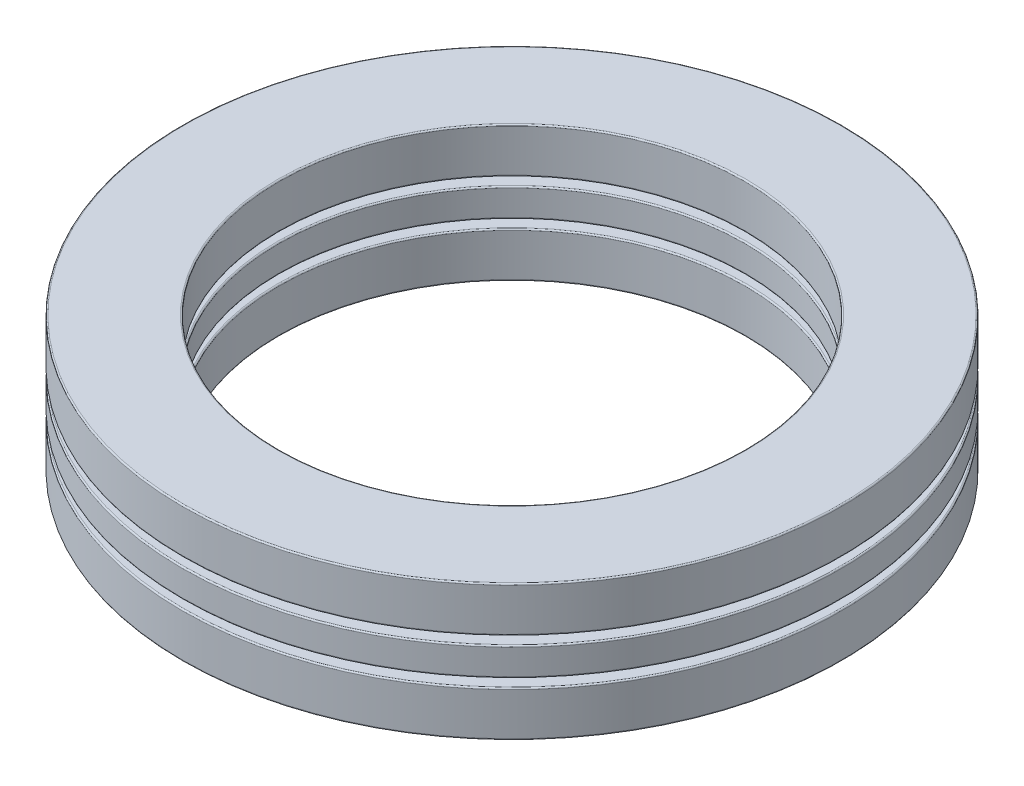
SolidWorks part; units mm, degrees
ref_plane "Front Plane" through (0, 0, 0) normal (0, 0, 1) x (1, 0, 0)
ref_plane "Top Plane" through (0, 0, 0) normal (0, 1, 0) x (1, 0, 0)
ref_plane "Right Plane" through (0, 0, 0) normal (1, 0, 0) x (0, 0, -1)
sketch "Sketch1" plane through (0, 0, 0) normal (1, 0, 0) x (0, 0, -1)
  line L0 (-26.9875, 0) -> (26.9875, 0) construction
  line L1 (0, -5.5499) -> (0, 5.5499) construction
  line L2 (-26.9875, 1.1562) -> (-19.0881, 1.1562)
  line L3 (-26.9875, 1.1562) -> (-26.9875, -1.1562)
  line L4 (-26.9875, -1.1562) -> (-19.0881, -1.1562)
  line L5 (-19.0881, 1.1562) -> (-19.0881, -1.1562)
  line L6 (-23.0378, 1.85) -> (-23.0378, -1.85) construction
  circle A0 centre (-23.0378, 0) radius 1.85 construction
  point P13 (-23.0378, 1.1562)
  dimension "OD" = 53.975
  dimension "Shaft Dia" = 38.1762
  dimension "Th" = 11.0998
  dimension "D1" = 3.6999
  dimension "D2" = 2.3125
revolve "Revolve1" add sketch "Sketch1" angle 360 about L1
sketch "Sketch3" plane through (0, 0, 0) normal (1, 0, 0) x (0, 0, -1)
  line L0 (-23.0378, 1.85) -> (-23.0378, -1.85)
  arc A0 (-23.0378, 1.85) -> (-23.0378, -1.85) centre (-23.0378, 0) ccw
  circle A1 centre (-23.0378, 0) radius 1.85 construction
revolve "Cut-Revolve1" cut sketch "Sketch3" angle 360 about L0
sketch "Sketch2" plane through (0, 0, 0) normal (1, 0, 0) x (0, 0, -1)
  line L0 (-23.0378, 1.85) -> (-23.0378, -1.85)
  arc A0 (-23.0378, 1.85) -> (-23.0378, -1.85) centre (-23.0378, 0) ccw
  circle A2 centre (-23.0378, 0) radius 1.85 construction
revolve "Revolve2" add sketch "Sketch2" angle 360 about L0
ref_axis "Axis1" through (0, 5.5499, 0) along (0, -1, 0)
pattern_circular "CirPattern1" count 11 every 32.727 about axis through (0, 5.5499, 0) along (0, -1, 0) of bodies 187
pattern_circular "CirPattern2" count 11 every 32.727 about axis through (0, 5.5499, 0) along (0, -1, 0) of "Cut-Revolve1"
sketch "Sketch4" plane through (0, 0, 0) normal (1, 0, 0) x (0, 0, -1)
  line L0 (-26.9875, 1.1562) -> (-26.9875, -1.1562) construction
  line L1 (-26.9875, 1.85) -> (-19.0881, 1.85)
  line L2 (-26.9875, 1.85) -> (-26.9875, 5.5499)
  line L3 (-26.9875, 5.5499) -> (-19.0881, 5.5499)
  line L4 (-19.0881, 1.85) -> (-19.0881, 5.5499)
  line L5 (-26.9875, -5.5499) -> (-19.0881, -5.5499)
  line L6 (-26.9875, -5.5499) -> (-26.9875, -1.85)
  line L7 (-26.9875, -1.85) -> (-19.0881, -1.85)
  line L8 (-19.0881, -5.5499) -> (-19.0881, -1.85)
  line L9 (-23.0378, 1.85) -> (-23.0378, -1.85) construction
  line L10 (-19.0881, 1.1562) -> (-19.0881, -1.1562) construction
  line L11 (0, 0) -> (-26.9875, 0) construction
  line L12 (-26.9875, 0) -> (26.9875, 0) construction
  dimension "Ht" = 11.0998
revolve "Revolve3" add sketch "Sketch4" angle 360 about L1
fillet "Fillet1" radius 0.111 4 edges at (0, 1.85, -19.0881) (0, 5.5499, -19.0881) (0, 1.85, -26.9875) (0, 5.5499, -26.9875)
fillet "Fillet2" radius 0.111 4 edges at (0, -1.1562, -19.0881) (0, 1.1562, -19.0881) (0, -1.1562, -26.9875) (0, 1.1562, -26.9875)
fillet "Fillet3" radius 0.111 4 edges at (0, -5.5499, -19.0881) (0, -1.85, -19.0881) (0, -5.5499, -26.9875) (0, -1.85, -26.9875)
equation "\"D1@Sketch1\" = \"Th@Sketch1\"/3"
equation "\"D2@Sketch1\" = \"D1@Sketch1\"*.625"
equation "\"Balls@CirPattern1\" = \"OD@Sketch1\"*5"
equation "\"Angle@CirPattern1\" = 360/\"Balls@CirPattern1\""
equation "\"D1@CirPattern2\" = \"Balls@CirPattern1\""
equation "\"D2@CirPattern2\" = \"Angle@CirPattern1\""
equation "\"D1@Fillet1\" = \"Th@Sketch1\"*.01"
equation "\"D1@Fillet2\" = \"D1@Fillet1\""
equation "\"D1@Fillet3\" = \"D1@Fillet1\""
